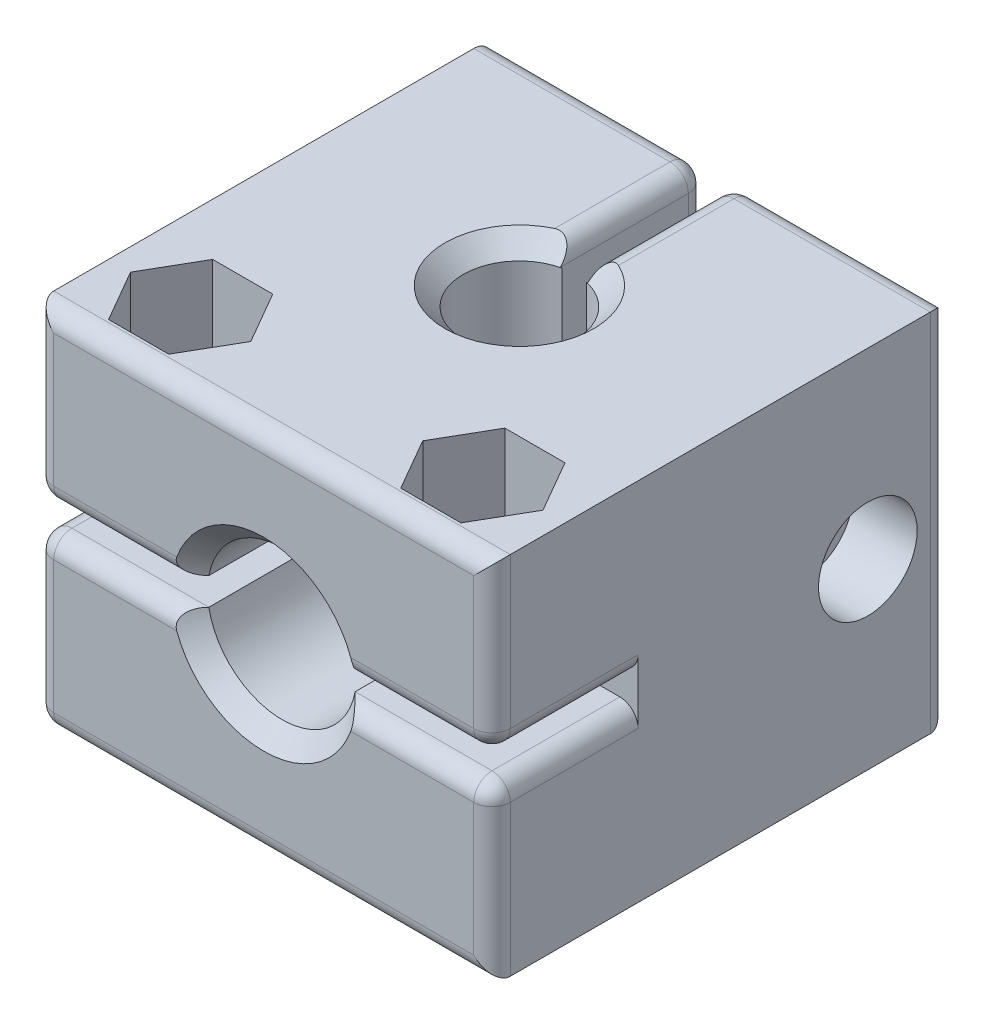
SolidWorks part; units mm, degrees
material "PLA"
ref_plane "Ebene vorne" through (0, 0, 0) normal (1, 0, 0) x (0, 1, 0)
ref_plane "Ebene oben" through (0, 0, 0) normal (0, 0, 1) x (0, 1, 0)
ref_plane "Ebene rechts" through (0, 0, 0) normal (0, 1, 0) x (-1, 0, 0)
sketch "Skizze1" plane through (0, 0, 0) normal (0, 0, 1) x (0, 1, 0)
  line L1 (-10, -12.5) -> (10, -12.5)
  line L2 (-10, -12.5) -> (-10, 12.5)
  line L3 (-10, 12.5) -> (10, 12.5)
  line L4 (10, -12.5) -> (10, 12.5)
  line L5 (-10, -12.5) -> (10, 12.5) construction
  line L6 (-10, 12.5) -> (10, -12.5) construction
  point P0 (0, 0)
  dimension "D1" = 20
  dimension "D2" = 25
extrude "Aufsatz-Linear austragen1" add sketch "Skizze1" along normal blind 25
sketch "Skizze2" plane through (0, -10, 0) normal (0, -1, 0) x (1, 0, 0)
  line L20 (-0.75, 0) -> (0.75, 0)
  line L21 (-0.75, 0) -> (-0.75, 8)
  line L22 (-0.75, 8) -> (0.75, 8)
  line L23 (0.75, 0) -> (0.75, 8)
  circle A0 centre (0, 0) radius 0.75 construction
  dimension "D1" = 8
  dimension "D2" = 1.5
extrude "Schnitt Pendel" cut sketch "Skizze2" against normal blind 20
sketch "Skizze3" plane through (0, -10, 0) normal (0, -1, 0) x (1, 0, 0)
  circle A1 centre (0, 11) radius 3.075
  dimension "D1" = 6.15
extrude "Loch Pendel" cut sketch "Skizze3" against normal blind 20 contours A1
sketch "Skizze6" plane through (0, 0, 25) normal (0, 0, 1) x (1, 0, 0)
  line L7 (12.5, -0.75) -> (12.5, 0.75)
  line L8 (12.5, -0.75) -> (-12.5, -0.75)
  line L9 (-12.5, -0.75) -> (-12.5, 0.75)
  line L10 (12.5, 0.75) -> (-12.5, 0.75)
  line L11 (12.5, -10) -> (12.5, 10) construction
  line L12 (-12.5, 10) -> (-12.5, -10) construction
extrude "Schnitt Welle" cut sketch "Skizze6" against normal blind 8
sketch "Skizze7" plane through (0, 0, 25) normal (0, 0, 1) x (1, 0, 0)
  circle A0 centre (0, 0) radius 4.075
  dimension "D1" = 8.15
extrude "Loch Welle" cut sketch "Skizze7" against normal blind 8
sketch "Skizze9" plane through (12.5, 0, 0) normal (1, 0, 0) x (0, 1, 0)
  line L0 (0, 0) -> (0, 6.84)
  line L1 (0, 0) -> (0, 2.4975)
  circle A1 centre (0, 4.42) radius 1.7
  dimension "D1" = 6.84
extrude "Schnitt-Linear austragen9" cut sketch "Skizze9" against normal blind 25 contours A1
sketch "Skizze10" plane through (12.5, 0, 0) normal (1, 0, 0) x (0, 1, 0)
  circle A0 centre (0, 4.42) radius 2.7
extrude "Schnitt-Linear austragen10" cut sketch "Skizze10" against normal blind 3.5
sketch "Skizze11" plane through (-12.5, 0, 0) normal (-1, 0, 0) x (0, -1, 0)
  line L1 (3.2909, 4.42) -> (1.6454, 7.27)
  line L2 (1.6454, 7.27) -> (-1.6454, 7.27)
  line L3 (-1.6454, 7.27) -> (-3.2909, 4.42)
  line L4 (-3.2909, 4.42) -> (-1.6454, 1.57)
  line L5 (-1.6454, 1.57) -> (1.6454, 1.57)
  line L6 (1.6454, 1.57) -> (3.2909, 4.42)
  circle A0 centre (0, 4.42) radius 2.85 construction
extrude "Schnitt-Linear austragen11" cut sketch "Skizze11" against normal blind 5
sketch "Skizze13" plane through (0, -10, 0) normal (0, -1, 0) x (1, 0, 0)
  line L1 (-12.5, 25) -> (-8, 25)
  line L2 (-12.5, 25) -> (-12.5, 21)
  line L3 (-12.5, 21) -> (-8, 21) construction
  line L4 (-8, 25) -> (-8, 21) construction
  line L5 (12.5, 25) -> (8, 25)
  line L6 (12.5, 25) -> (12.5, 21)
  line L7 (12.5, 21) -> (8, 21)
  line L8 (8, 25) -> (8, 21)
  circle A0 centre (-8, 21) radius 1.7
  circle A1 centre (8, 21) radius 1.7
  dimension "D1" = 4
  dimension "D2" = 4.5
extrude "Schnitt-Linear austragen12" cut sketch "Skizze13" against normal blind 25 contours A0 | A1
sketch "Skizze15" plane through (0, -10, 0) normal (0, -1, 0) x (1, 0, 0)
  circle A0 centre (-8, 21) radius 2.7
  circle A1 centre (8, 21) radius 2.7
extrude "Schnitt-Linear austragen13" cut sketch "Skizze15" against normal blind 3.5
sketch "Skizze16" plane through (0, 10, 0) normal (0, 1, 0) x (-1, 0, 0)
  line L1 (12.5, 25) -> (8, 25) construction
  line L2 (12.5, 25) -> (12.5, 21) construction
  line L3 (12.5, 21) -> (8, 21) construction
  line L4 (8, 25) -> (8, 21) construction
  line L5 (11.2909, 21) -> (9.6454, 23.85)
  line L6 (9.6454, 23.85) -> (6.3546, 23.85)
  line L7 (6.3546, 23.85) -> (4.7091, 21)
  line L8 (4.7091, 21) -> (6.3546, 18.15)
  line L9 (6.3546, 18.15) -> (9.6454, 18.15)
  line L10 (9.6454, 18.15) -> (11.2909, 21)
  line L15 (-4.7091, 21) -> (-6.3546, 23.85)
  line L16 (-6.3546, 23.85) -> (-9.6454, 23.85)
  line L17 (-9.6454, 23.85) -> (-11.2909, 21)
  line L18 (-11.2909, 21) -> (-9.6454, 18.15)
  line L19 (-9.6454, 18.15) -> (-6.3546, 18.15)
  line L20 (-6.3546, 18.15) -> (-4.7091, 21)
  circle A0 centre (8, 21) radius 2.85 construction
  circle A1 centre (-8, 21) radius 2.85 construction
  dimension "D1" = 4
  dimension "D2" = 4.5
extrude "Schnitt-Linear austragen14" cut sketch "Skizze16" against normal blind 5
chamfer "Fase1" distance 1 angle 45 4 edges at (0, -10, 14.075) (0, 4.075, 25) (0, -4.075, 25) (0, 10, 14.075)
fillet "Verrundung5" radius 1 14 edges at (12.5, 0.75, 21) (12.5, -0.75, 21) (-12.5, 0.75, 21) (-12.5, -0.75, 21) (-0.75, 10, 3.4973) (0.75, 10, 3.4973) (-0.75, -10, 3.4973) (0.75, -10, 3.4973) (-0.75, 0, 0) (0.75, 0, 0) (-8.7596, 0.75, 25) (-8.7596, -0.75, 25) (8.7596, 0.75, 25) (8.7596, -0.75, 25)
fillet "Verrundung6" radius 1 20 edges at (-1.0429, 9.7071, 0.2929) (1.0429, 9.7071, 0.2929) (-1.0429, -9.7071, 0.2929) (1.0429, -9.7071, 0.2929) (-12.2071, -1.0429, 24.7071) (-12.2071, 1.0429, 24.7071) (12.2071, 1.0429, 24.7071) (12.2071, -1.0429, 24.7071) (-12.5, -10, 12.5) (-7.125, 10, 0) (7.125, 10, 0) (-7.125, -10, 0) (7.125, -10, 0) (12.5, 0, 0) (-12.5, -5.875, 25) (-12.5, 5.875, 25) (0, 10, 25) (12.5, 5.875, 25) (12.5, -5.875, 25) (0, -10, 25)
